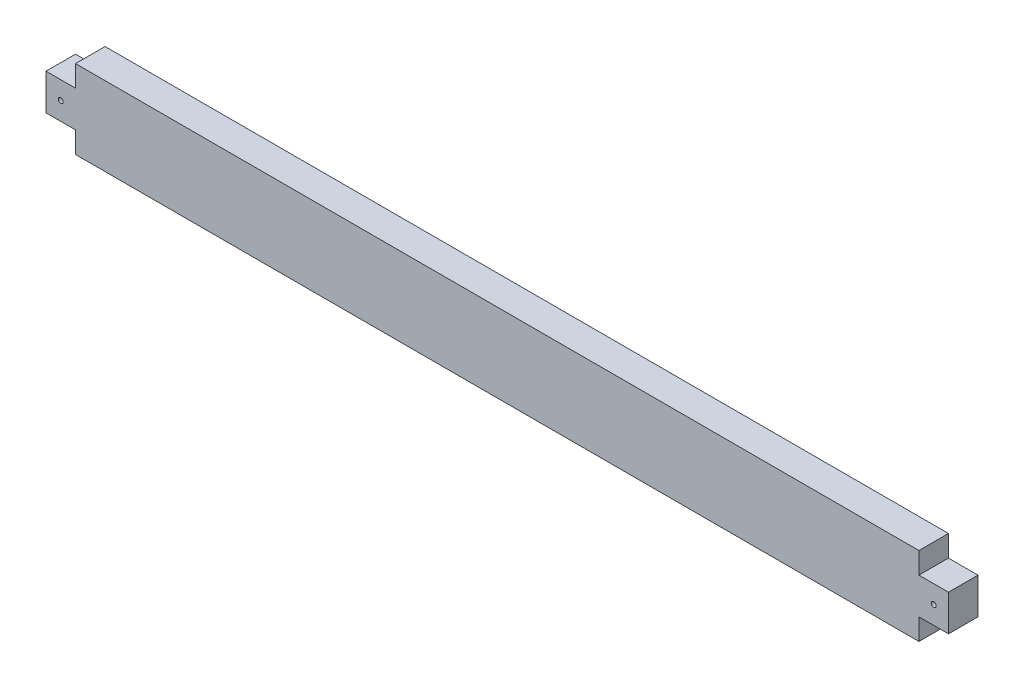
SolidWorks part; units mm, degrees
material "Teak"
ref_plane "Front Plane" through (0, 0, 0) normal (0, 0, 1) x (1, 0, 0)
ref_plane "Top Plane" through (0, 0, 0) normal (0, 1, 0) x (1, 0, 0)
ref_plane "Right Plane" through (0, 0, 0) normal (1, 0, 0) x (0, 0, -1)
sketch "Sketch1" plane through (0, 0, 0) normal (0, 0, 1) x (1, 0, 0)
  line L1 (-275, 24) -> (275, 24)
  line L2 (-275, 24) -> (-275, -24)
  line L3 (-275, -24) -> (275, -24)
  line L4 (275, 24) -> (275, -24)
  line L5 (-275, 24) -> (275, -24) construction
  line L6 (-275, -24) -> (275, 24) construction
  point P0 (0, 0)
  dimension "D1" = 550
  dimension "D2" = 48
extrude "Основа" add sketch "Sketch1" along normal blind 18
sketch "Sketch2" plane through (0, 0, 18) normal (0, 0, 1) x (1, 0, 0)
  line L0 (-275, -11) -> (-257, -11)
  line L1 (-275, 24) -> (-275, -24) construction
  line L2 (-257, -11) -> (-257, 11) construction
  line L3 (-257, 11) -> (-275, 11)
  line L4 (-275, 11) -> (-275, -11) construction
  line L5 (0, 24) -> (0, -24) construction
  line L6 (275, 24) -> (-275, 24) construction
  line L7 (-275, -24) -> (275, -24) construction
  line L8 (-275, -11) -> (-275, -24)
  line L9 (-275, -24) -> (-257, -24)
  line L10 (-257, -24) -> (-257, -11)
  line L11 (-275, 24) -> (-275, 11)
  line L12 (-257, 11) -> (-257, 24)
  line L13 (-257, 24) -> (-275, 24)
  point P13 (-275, 0)
  point P14 (-275, 0)
  dimension "D1" = 18
  dimension "D2" = 22
extrude "Шип" cut sketch "Sketch2" against normal up to next
sketch "Sketch3" plane through (0, 0, 18) normal (0, 0, 1) x (1, 0, 0)
  line L3 (-275, 11) -> (-257, 11) construction
  line L4 (-275, 11) -> (-275, -11) construction
  circle A2 centre (-266, 0) radius 1.5
  point P2 (0, 0)
  point P5 (-266, 11)
  point P6 (0, 0)
  point P9 (-275, 0)
  dimension "D1" = 3
extrude "Крепежные" cut sketch "Sketch3" against normal up to next
mirror "Mirror1" about plane through (0, 0, 0) normal (1, 0, 0) of "Крепежные", "Шип"
